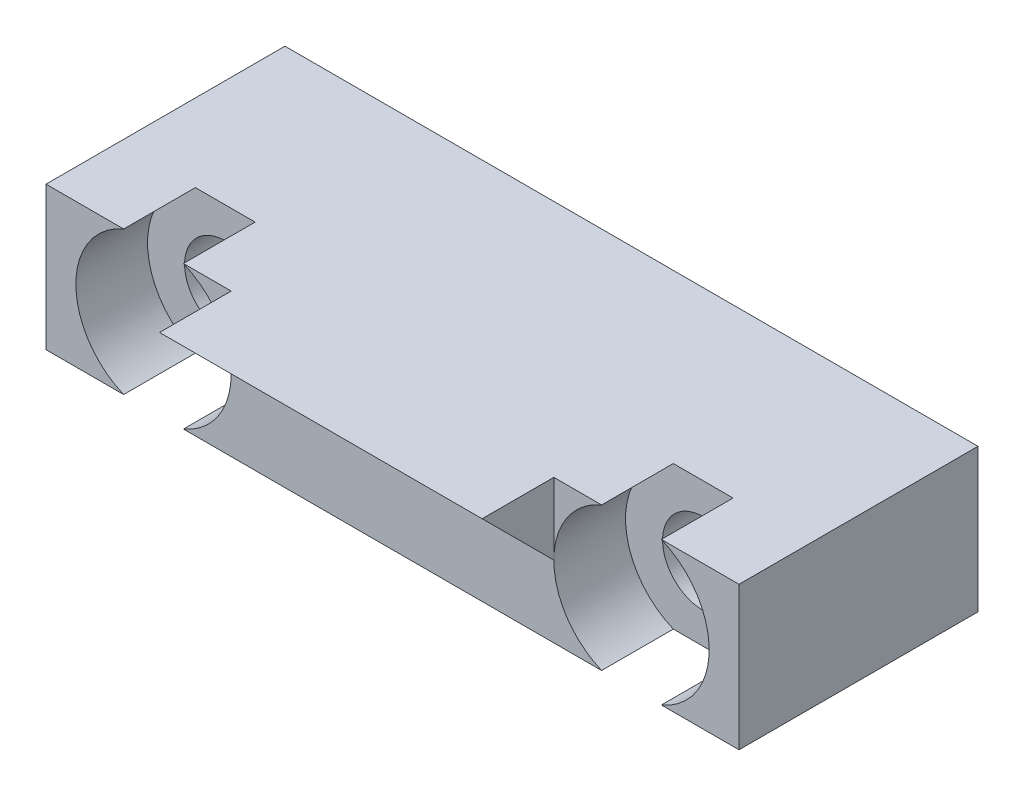
SolidWorks part; units mm, degrees
ref_plane "Front Plane" through (0, 0, 0) normal (0, 0, 1) x (1, 0, 0)
ref_plane "Top Plane" through (0, 0, 0) normal (0, 1, 0) x (1, 0, 0)
ref_plane "Right Plane" through (0, 0, 0) normal (1, 0, 0) x (0, 0, -1)
sketch "Sketch1" plane through (0, 0, 0) normal (0, 0, 1) x (1, 0, 0)
  line L1 (-14.5, -3) -> (14.5, -3)
  line L2 (-14.5, -3) -> (-14.5, 3)
  line L3 (-14.5, 3) -> (14.5, 3)
  line L4 (14.5, -3) -> (14.5, 3)
  line L5 (-14.5, -3) -> (14.5, 3) construction
  line L6 (-14.5, 3) -> (14.5, -3) construction
  point P0 (0, 0)
  dimension "D1" = 6
  dimension "D2" = 29
extrude "Boss-Extrude1" add sketch "Sketch1" along normal blind 10
sketch "Sketch5" plane through (0, 0, 10) normal (0, 0, 1) x (1, 0, 0)
  line L1 (-6.75, 3) -> (6.75, 3)
  line L2 (-6.75, 3) -> (-6.75, 0)
  line L3 (-6.75, 0) -> (6.75, 0)
  line L4 (6.75, 3) -> (6.75, 0)
  line L6 (14.5, 3) -> (-14.5, 3) construction
  point P5 (0, 0)
  point P6 (0, 0)
  dimension "D1" = 3
  dimension "D2" = 13.5
extrude "Boss-Extrude2" add sketch "Sketch5" along normal blind 3
hole_wizard "CBORE for M3 SHCS1" positions "Sketch2" profile "Sketch4" counterbore size "M3" standard "ANSI Metric" end condition through all
sketch "Sketch2" plane through (0, 0, 10) normal (0, 0, 1) x (1, 0, 0)
  line L0 (-10, 0) -> (10, 0)
  point P1 (-10, 0)
  point P2 (10, 0)
  point P4 (0, 0)
  dimension "D1" = 20
sketch "Sketch4" plane through (-10, 0, 10) normal (1, 0, 0) x (0, -1, 0)
  line L0 (0, 0) -> (0, 10)
  line L1 (0, 10) -> (1.7, 10)
  line L3 (1.7, 10) -> (1.7, 3)
  line L4 (1.7, 3) -> (3.25, 3)
  line L5 (3.25, 3) -> (3.25, 0)
  line L7 (3.25, 0) -> (0, 0)
  line L11 (0, -6.35) -> (0, 107.95) construction
  dimension "Thru Hole Dia." = 3.4
  dimension "Thru Hole Depth" = 10
  dimension "C'Bore Dia." = 6.5
  dimension "C'Bore Depth" = 3
chamfer "Chamfer1" distance 3 angle 45 1 edges at (0, 0, 13)
